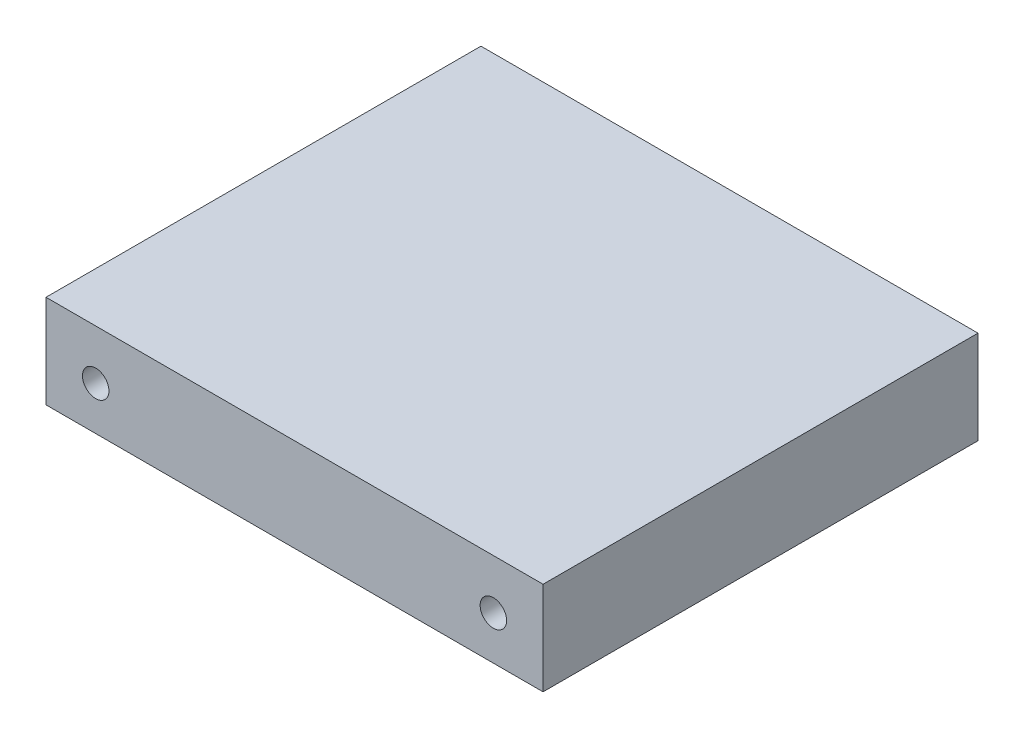
SolidWorks part; units mm, degrees
ref_plane "Front Plane" through (0, 0, 0) normal (0, 0, 1) x (1, 0, 0)
ref_plane "Top Plane" through (0, 0, 0) normal (0, 1, 0) x (1, 0, 0)
ref_plane "Right Plane" through (0, 0, 0) normal (1, 0, 0) x (0, 0, -1)
sketch "Sketch2" plane through (0, 0, 0) normal (0, 1, 0) x (1, 0, 0)
  line L1 (-25.4, 22.225) -> (25.4, 22.225)
  line L2 (-25.4, 22.225) -> (-25.4, -22.225)
  line L3 (-25.4, -22.225) -> (25.4, -22.225)
  line L4 (25.4, 22.225) -> (25.4, -22.225)
  line L5 (-25.4, 22.225) -> (25.4, -22.225) construction
  line L6 (-25.4, -22.225) -> (25.4, 22.225) construction
  point P0 (0, 0)
  dimension "D1" = 50.8
  dimension "D2" = 44.45
extrude "Boss-Extrude1" add sketch "Sketch2" along normal blind 9.525 contours L2 L3 L4 L1
sketch "Sketch3" plane through (0, 0, 22.225) normal (0, 0, 1) x (1, 0, 0)
  circle A0 centre (20.32, 4.445) radius 1.8415
  circle A1 centre (-20.32, 4.445) radius 1.8415
hole_wizard "#6-32 Tapped Hole1" positions "Sketch4" profile "Sketch5" tap size "#6-32" standard "ANSI Inch"
sketch "Sketch4" plane through (0, 0, 22.225) normal (0, 0, 1) x (1, 0, 0)
  point P0 (-20.32, 4.445)
  point P2 (20.32, 4.445)
sketch "Sketch5" plane through (-20.32, 4.445, 22.225) normal (1, 0, 0) x (0, -1, 0)
  line L0 (0, 0) -> (0, 10.2107)
  line L1 (0, 10.2107) -> (1.3525, 9.398)
  line L2 (1.3525, 9.398) -> (1.3525, 0)
  line L5 (1.3525, 0) -> (0, 0)
  line L10 (0, 10.2107) -> (-1.3526, 9.398) construction
  line L11 (0, -6.35) -> (0, 107.95) construction
  dimension "Tap Drill Dia." = 2.7051
  dimension "Tap Drill Depth" = 9.398
  dimension "Drill Angle" = 118
cosmetic thread "Hole Thread1" parameters "D1"=7.112, "D2"=3.5052
cosmetic thread "Hole Thread2" parameters "D1"=7.112, "D2"=3.5052
hole_wizard "#6-32 Tapped Hole2" positions "Sketch6" profile "Sketch7" tap size "#6-32" standard "ANSI Inch"
sketch "Sketch6" plane through (0, 0, -22.225) normal (0, 0, -1) x (-1, 0, 0)
  point P0 (-20.32, 4.445)
  point P2 (20.32, 4.445)
sketch "Sketch7" plane through (20.32, 4.445, -22.225) normal (1, 0, 0) x (0, 1, 0)
  line L0 (0, 0) -> (0, 10.2107)
  line L1 (0, 10.2107) -> (1.3525, 9.398)
  line L2 (1.3525, 9.398) -> (1.3525, 0)
  line L5 (1.3525, 0) -> (0, 0)
  line L10 (0, 10.2107) -> (-1.3525, 9.398) construction
  line L11 (0, -6.35) -> (0, 107.95) construction
  dimension "Tap Drill Dia." = 2.7051
  dimension "Tap Drill Depth" = 9.398
  dimension "Drill Angle" = 118
cosmetic thread "Hole Thread3" parameters "D1"=7.112, "D2"=3.5052
cosmetic thread "Hole Thread4" parameters "D1"=7.112, "D2"=3.5052
